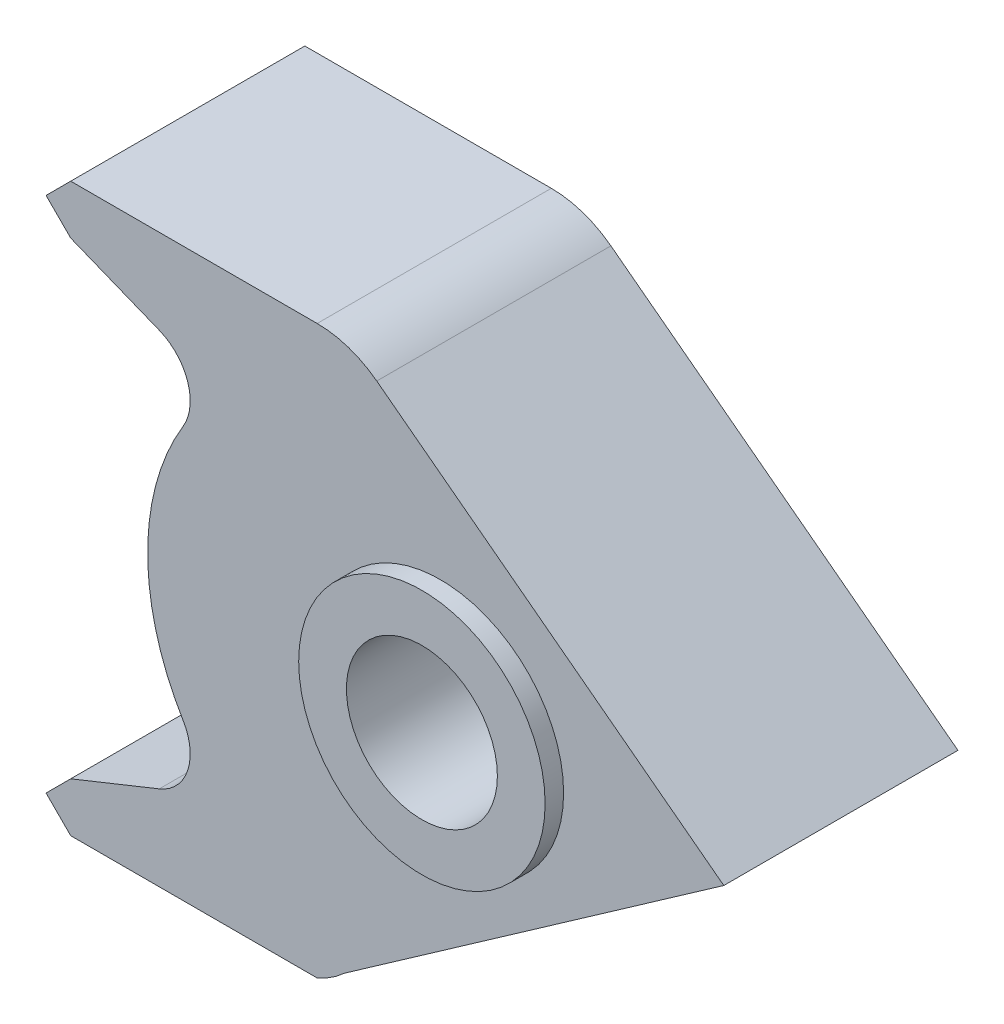
SolidWorks part; units mm, degrees
ref_plane "Plano frontal" through (0, 0, 0) normal (0, 0, 1) x (1, 0, 0)
ref_plane "Plano superior" through (0, 0, 0) normal (0, 1, 0) x (1, 0, 0)
ref_plane "Plano direito" through (0, 0, 0) normal (1, 0, 0) x (0, 0, -1)
sketch "Esboço1" plane through (0, 0, 0) normal (0, 0, 1) x (1, 0, 0)
  line L1 (0, 0) -> (-28.1639, 21.3728)
  line L2 (-33, 23) -> (-53, 23)
  line L3 (-53, 23) -> (-55, 21)
  line L4 (-55, 21) -> (-53, 19)
  line L5 (-53, 19) -> (-45.812, 16.1148)
  line L6 (-53, -19) -> (-45.812, -16.1148)
  line L7 (-55, -21) -> (-53, -19)
  line L8 (-53, -23) -> (-55, -21)
  line L9 (-33, -23) -> (-53, -23)
  line L10 (0, 0) -> (-30.7812, -21.5532)
  line L11 (0, 0) -> (87.2743, 0)
  circle A0 centre (-23, 0) radius 6.125
  arc A1 (-28.1639, 21.3728) -> (-33, 23) centre (-33, 15) ccw
  arc A2 (-43.8776, 10.3356) -> (-43.8776, -10.3356) centre (-26.7552, 0) ccw
  arc A3 (-45.812, 16.1148) -> (-43.8776, 10.3356) centre (-47.302, 12.4027) cw
  arc A5 (-45.812, -16.1148) -> (-43.8776, -10.3356) centre (-47.302, -12.4027) ccw
  arc A6 (-30.7812, -21.5532) -> (-33, -23) centre (-36.1999, -15.6678) cw
  point P11 (-30.3082, 23)
  point P19 (-40.8973, 14.1421)
  point P28 (-43.2671, -14.1421)
  point P29 (-32.8474, -23)
  dimension "D1" = 12.25
  dimension "D5" = 8
  dimension "D8" = 20
  dimension "D9" = 4
  dimension "D2" = 55
  dimension "D3" = 23
  dimension "D6" = 90
  dimension "D7" = 4
  dimension "D10" = 20
extrude "Ressalto-extrusão1" add sketch "Esboço1" along normal blind 22 contours A6 L10 L1 A1 L2 L3 L4 L5 A3 A2 A5 L6 L7 L8 L9 A0 region at (-31.0267, 0.3233, 0)
sketch "Esboço2" plane through (0, 0, 22) normal (0, 0, 1) x (1, 0, 0)
  circle A0 centre (-23, 0) radius 10
  dimension "D1" = 20
extrude "Corte-extrusão1" cut sketch "Esboço2" against normal blind 1.5 flip side to cut
sketch "Esboço3" plane through (0, 0, 0) normal (0, 0, -1) x (-1, 0, 0)
  circle A0 centre (23, 0) radius 10
  dimension "D1" = 20
extrude "Corte-extrusão2" cut sketch "Esboço3" against normal blind 1.5 flip side to cut
